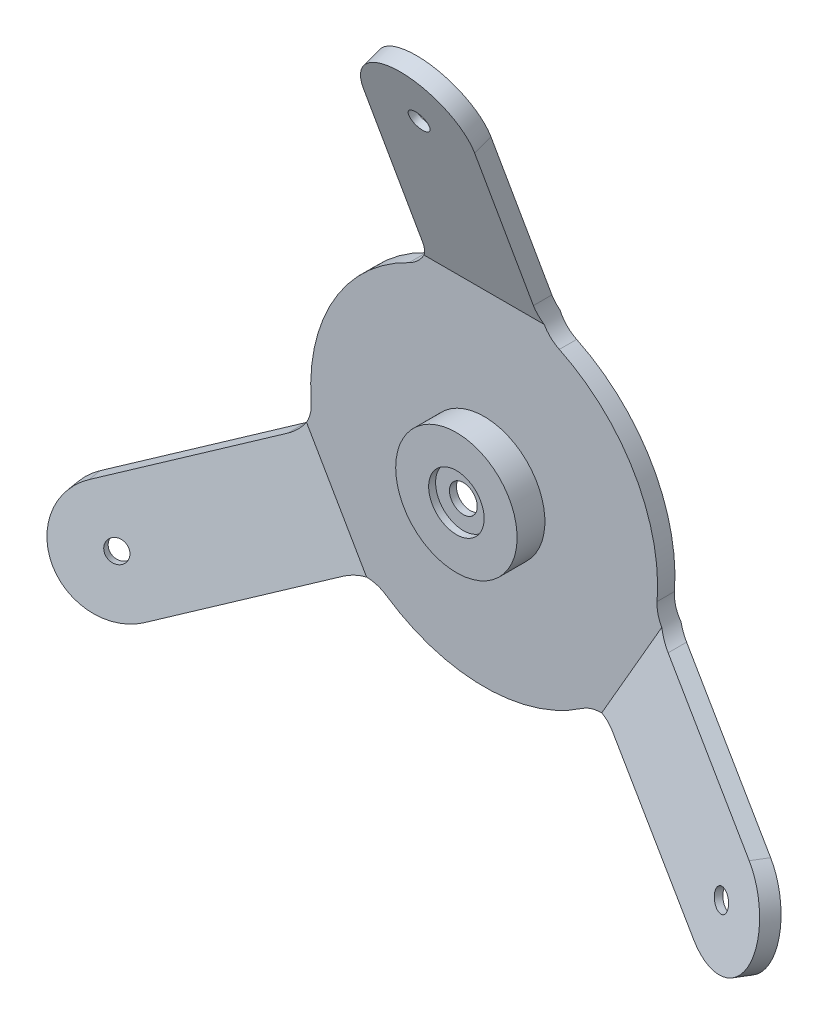
SolidWorks part; units mm, degrees
ref_plane "前视基准面" through (0, 0, 0) normal (0, 0, 1) x (1, 0, 0)
ref_plane "上视基准面" through (0, 0, 0) normal (0, 1, 0) x (1, 0, 0)
ref_plane "右视基准面" through (0, 0, 0) normal (1, 0, 0) x (0, 0, -1)
sketch "草图1" plane through (0, 0, 0) normal (0, 0, 1) x (1, 0, 0)
  line L0 (0, 0) -> (0, 109.2545) construction
  line L1 (0, 0) -> (94.6172, -54.6272) construction
  line L2 (0, 0) -> (-94.6172, -54.6272) construction
  line L3 (43.3013, -25) -> (33.8266, -41.4106) construction
  line L4 (33.8266, -41.4106) -> (51.4101, -10.9552) construction
  circle A0 centre (0, 0) radius 50
  circle A1 centre (0, 0) radius 17.5
  circle A2 centre (0, 0) radius 109.2545
  point P10 (0, 0)
  dimension "D1" = 3
extrude "凸台-拉伸1" add sketch "草图1" along normal blind 5 contours A0
extrude "凸台-拉伸2" add sketch "草图1<3>" along normal blind 13 contours A1
sketch "草图1<3>" plane through (0, 0, 0) normal (0, 0, 1) x (1, 0, 0) same geometry as "草图1"
sketch "草图2" plane through (0, 0, 13) normal (0, 0, 1) x (1, 0, 0)
  circle A0 centre (0, 0) radius 8
extrude "切除-拉伸1" cut sketch "草图2" against normal blind 2
ref_plane "基准面1" through (5.0653, -2.9244, -16.0697) normal (0.2962, -0.171, -0.9397) x (-0.4548, 0.8399, -0.2962)
sketch "草图3" plane through (5.0653, -2.9244, -16.0697) normal (0.2962, -0.171, -0.9397) x (-0.4548, 0.8399, -0.2962)
  line L0 (-48.6899, 9.6359) -> (-44.1707, 7.0268)
  line L1 (-32.6899, 37.3487) -> (-80.911, 65.1892)
  line L2 (-48.6899, 9.6359) -> (-96.911, 37.4764)
  line L4 (-32.6899, 37.3487) -> (-28.1707, 34.7396)
  line L5 (-28.1707, 34.7396) -> (-44.1707, 7.0268)
  arc A0 (-80.911, 65.1892) -> (-96.911, 37.4764) centre (-88.911, 51.3328) ccw
extrude "凸台-拉伸3" add sketch "草图3" against normal blind 5
sketch "草图4" plane through (33.9894, -19.6238, 14.2849) normal (-0.8138, 0.4698, -0.342) x (-0.2962, 0.171, 0.9397)
  line L0 (-17.101, 16) -> (-15.2017, 16)
  line L1 (-15.2017, 16) -> (-15.2017, -16)
  line L2 (-15.2017, -16) -> (-17.101, -16)
  line L3 (-17.101, -16) -> (-17.101, 16)
ref_plane "基准面2" through (38.4921, -22.2234, 0) normal (0.866, -0.5, 0) x (0, 0, -1)
sketch "草图5" plane through (38.4921, -22.2234, 0) normal (0.866, -0.5, 0) x (0, 0, -1)
  line L0 (0, 16) -> (0, -16)
  line L1 (0, -16) -> (1.7848, -16)
  line L2 (1.7848, -16) -> (1.7848, 16)
  line L3 (1.7848, 16) -> (0, 16)
extrude "凸台-拉伸5" add sketch "草图3<3>" against normal up to surface (5.3209 mm away) contours L0 L5 L4 L1 A0 L2 up to face at (17.5, 0, 5)
sketch "草图3<3>" plane through (5.0653, -2.9244, -16.0697) normal (0.2962, -0.171, -0.9397) x (-0.4548, 0.8399, -0.2962) same geometry as "草图3"
extrude "切除-拉伸2" cut sketch "草图5" along normal through all
fillet "圆角5" radius 10 2 edges at (49.0244, -9.829, 2.5) (33.0244, -37.5418, 2.5)
ref_axis "基准轴1" through (0, 0, 13) along (0, 0, -1)
pattern_circular "阵列(圆周)5" count 3 over 360 about axis through (0, 0, 13) along (0, 0, -1) of "凸台-拉伸3", "凸台-拉伸5", "圆角5", "切除-拉伸2"
shell "抽壳1" thickness 2 removed face at (-61.7386, -35.6448, 7.7488) removed face at (61.7386, -35.6448, 7.7488) removed face at (0, 0, 0) removed face at (0, 71.2896, 7.7488)
sketch "草图6" plane through (0, 4.1388, -11.3712) normal (0, -0.342, 0.9397) x (1, 0, 0)
  circle A0 centre (0, 102.6656) radius 3
extrude "切除-拉伸3" cut sketch "草图6" against normal through all
pattern_circular "阵列(圆周)6" count 3 every 120 about axis through (0, 0, 13) along (0, 0, -1) of "切除-拉伸3"
sketch "草图7" plane through (0, 0, 11) normal (0, 0, 1) x (1, 0, 0)
  circle A0 centre (0, 0) radius 4
extrude "切除-拉伸4" cut sketch "草图7" against normal through all
